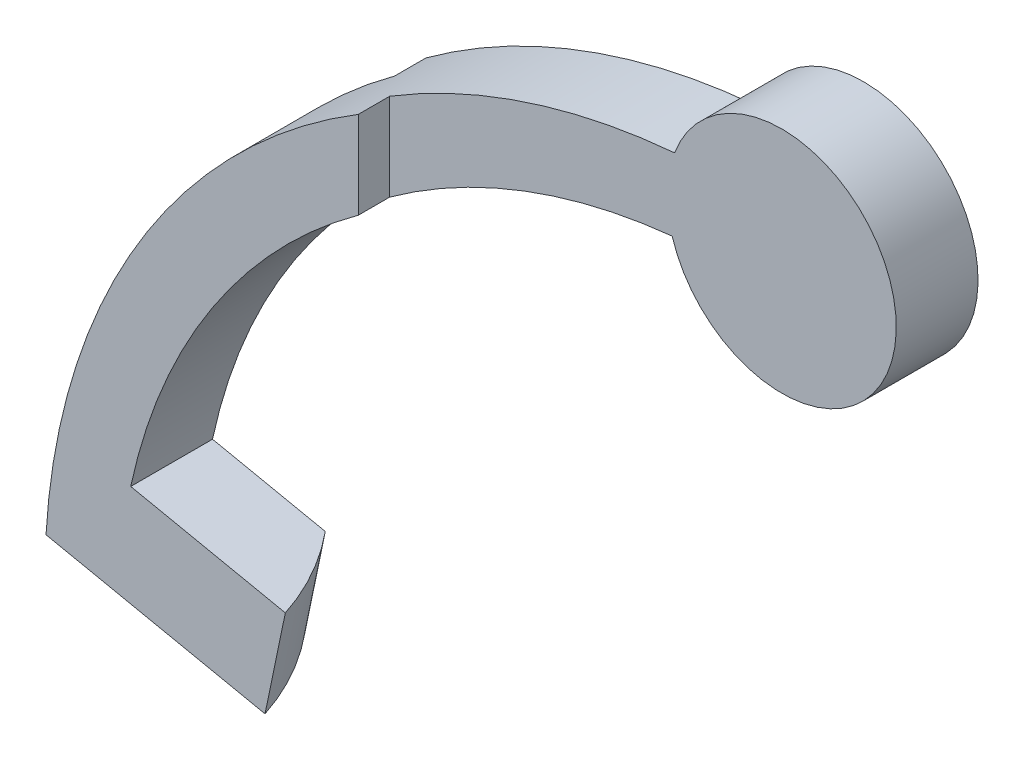
SolidWorks part; units mm, degrees
ref_plane "Front Plane" through (0, 0, 0) normal (0, 0, 1) x (1, 0, 0)
ref_plane "Top Plane" through (0, 0, 0) normal (0, 1, 0) x (1, 0, 0)
ref_plane "Right Plane" through (0, 0, 0) normal (1, 0, 0) x (0, 0, -1)
sketch "Esquisse3" plane through (0, 0, 0) normal (0, 0, 1) x (1, 0, 0)
  line L0 (-43.0597, -35.0596) -> (-29.6704, -37.8465)
  line L1 (-29.6704, -37.8465) -> (-28.4288, -31.8813)
  line L2 (-28.4288, -31.8813) -> (-37.881, -29.9139)
  circle A0 centre (0, 0) radius 7
  arc A1 (-6.5562, 2.4527) -> (-43.0597, -35.0596) centre (-3.1282, -37.4001) ccw
  arc A2 (-37.881, -29.9139) -> (-6.6992, -2.0301) centre (-3.1282, -37.4001) cw
  dimension "D1" = 14
  dimension "D2" = 40
extrude "Boss.-Extru.2" add sketch "Esquisse3" along normal blind 5 contours A0 region at (0, 0, 0)
extrude "Boss.-Extru.3" add sketch "Esquisse3<3>" along normal blind 45 contours L2 A2 A0 A1 L0 L1 region at (-31.4057, -9.8832, 0)
sketch "Esquisse3<3>" plane through (0, 0, 0) normal (0, 0, 1) x (1, 0, 0) same geometry as "Esquisse3"
sketch "Esquisse4" plane through (0, 0, 0) normal (0, 1, 0) x (1, 0, 0)
  line L0 (-6.5562, 0) -> (-6.5562, -5)
  line L4 (-6.5562, -5) -> (-6.5562, 0) construction
  line L6 (-6.5562, -45) -> (-6.5562, -5) construction
  line L8 (-6.5562, -21.6438) -> (-6.5562, -5)
  line L10 (-43.0597, -11.9185) -> (-43.0597, -53.527)
  line L11 (-43.0597, -53.527) -> (-6.4252, -53.527)
  line L12 (-6.4252, -53.527) -> (-6.5562, -21.6438)
  line L13 (-43.0597, -11.9185) -> (-43.0597, -6.9185)
  line L14 (-43.0597, -45) -> (-43.0597, 0) construction
  line L15 (-6.5562, 0) -> (-43.0597, 0) construction
  line L16 (-43.0597, -45) -> (-43.0597, 0)
  line L17 (-6.5562, 0) -> (-43.0597, 0)
  line L18 (-26.7522, 0) -> (-26.7522, -1.9185)
  line L19 (-26.7522, -1.9185) -> (-43.0597, -1.9185)
  line L20 (-43.0597, -1.9185) -> (-43.0597, -6.9185)
  line L21 (-43.0597, -6.9185) -> (-23.9674, -6.9185)
  line L22 (-23.9674, -6.9185) -> (-23.9674, -5)
  line L23 (-23.9674, -5) -> (-6.5562, -5)
  point P4 (0, 0)
  dimension "D2" = 5
extrude "Enlèv. mat.-Extru.3" cut sketch "Esquisse4" against normal through all and the other way blind 5 contours L8 region at (-24.6024, 0, 29.7714)
extrude "Enlèv. mat.-Extru.4" cut sketch "Esquisse4<4>" against normal through all contours L19 L18 L17 L16 region at (-34.906, 0, 0.9592)
sketch "Esquisse4<4>" plane through (0, 0, 0) normal (0, 1, 0) x (1, 0, 0) same geometry as "Esquisse4"
sketch "Esquisse5" plane through (-7.5408, -36.229, 0) normal (0.2038, 0.979, 0) x (0.979, -0.2038, 0)
  line L0 (-30.9904, -1.9185) -> (-21.3357, -1.9185) construction
  line L1 (-23.9488, -1.9185) -> (-21.3357, -1.9185)
  line L2 (-21.3357, -1.9185) -> (-21.3357, -6.9185)
  arc A1 (-21.3357, -6.9185) -> (-23.9488, -1.9185) centre (-34.8747, -10.8114) ccw
extrude "Enlèv. mat.-Extru.6" cut sketch "Esquisse5" against normal through all
